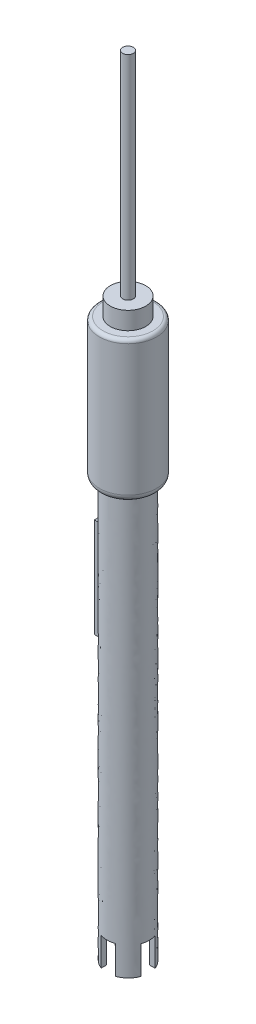
SolidWorks part; units mm, degrees
ref_plane "Alzado" through (0, 0, 0) normal (0, 0, 1) x (1, 0, 0)
ref_plane "Planta" through (0, 0, 0) normal (0, 1, 0) x (1, 0, 0)
ref_plane "Vista lateral" through (0, 0, 0) normal (1, 0, 0) x (0, 0, -1)
sketch "Croquis1" plane through (0, 0, 0) normal (0, 0, 1) x (1, 0, 0)
  line L0 (0, 0) -> (6.25, 0)
  line L1 (6.25, 0) -> (6.25, 117.5)
  line L2 (6.25, 117.5) -> (8.075, 117.5)
  line L3 (8.075, 117.5) -> (8.075, 157.5)
  line L4 (8.075, 157.5) -> (0, 157.5)
  line L5 (0, 157.5) -> (0, 0)
  line L6 (0, 0) -> (0, -88.7977) construction
  dimension "D1" = 117.5
  dimension "D2" = 12.5
  dimension "D3" = 16.15
  dimension "D4" = 40
revolve "Revolución1" add sketch "Croquis1" angle 360 about L6
fillet "Redondeo1" radius 2 1 edges at (0, 117.5, 8.075)
sketch "Croquis2" plane through (0, 157.5, 0) normal (0, 1, 0) x (1, 0, 0)
  circle A0 centre (0, 0) radius 5
  dimension "D1" = 10
extrude "Saliente-Extruir1" add sketch "Croquis2" along normal blind 5
fillet "Redondeo2" radius 1 1 edges at (0, 157.5, 8.075)
sketch "Croquis3" plane through (0, 162.5, 0) normal (0, 1, 0) x (1, 0, 0)
  circle A0 centre (0, 0) radius 1.5
  dimension "D1" = 3
extrude "Saliente-Extruir2" add sketch "Croquis3" along normal blind 60
sketch "Croquis4" plane through (0, 0, 0) normal (0, -1, 0) x (1, 0, 0)
  line L1 (-8.075, -8.075) -> (8.075, -8.075)
  line L2 (-8.075, -8.075) -> (-8.075, 8.075)
  line L3 (-8.075, 8.075) -> (8.075, 8.075)
  line L4 (8.075, -8.075) -> (8.075, 8.075)
  line L5 (-8.075, -8.075) -> (8.075, 8.075) construction
  line L6 (-8.075, 8.075) -> (8.075, -8.075) construction
  circle A0 centre (0, 0) radius 8.075 construction
  ellipse E0 centre (0, 0) end of major axis (-6, 0) minor radius 5.9
  dimension "D1" = 11.8
  dimension "D2" = 12
extrude "Cortar-Extruir1" cut sketch "Croquis4" against normal blind 117.5
sketch "Croquis5" plane through (0, 0, 0) normal (1, 0, 0) x (0, 0, -1)
  line L1 (3, 106) -> (-3, 106)
  line L2 (3, 106) -> (3, 78)
  line L3 (3, 78) -> (-3, 78)
  line L4 (-3, 106) -> (-3, 78)
  line L5 (3, 106) -> (-3, 78) construction
  line L6 (3, 78) -> (-3, 106) construction
  point P0 (0, 92)
  dimension "D1" = 78
  dimension "D2" = 28
  dimension "D3" = 6
extrude "Saliente-Extruir3" add sketch "Croquis5" against normal blind 6.5
sketch "Croquis6" plane through (0, 0, 0) normal (0, -1, 0) x (1, 0, 0)
  line L0 (6, 0) -> (-6, 0)
  line L1 (0, 5.9) -> (0, -5.9)
  ellipse E0 centre (0, 0) end of major axis (-6, 0) minor radius 5.9 construction
  ellipse E1 centre (0, 0) end of major axis (-6, 0) minor radius 5.9 construction
  point P17 (0, 0)
  point P21 (0, 0)
extrude "Cortar-Extruir-Lámina1" cut sketch "Croquis6" against normal blind 8 thin thin type mid plane wall 4
sketch "Croquis7" plane through (0, 0, 0) normal (0, -1, 0) x (1, 0, 0)
  circle A0 centre (0, 0) radius 4.5
  dimension "D1" = 9
extrude "Cortar-Extruir2" cut sketch "Croquis7" against normal up to vertex (8 mm away) up to point (2, 8, 5.5626)
